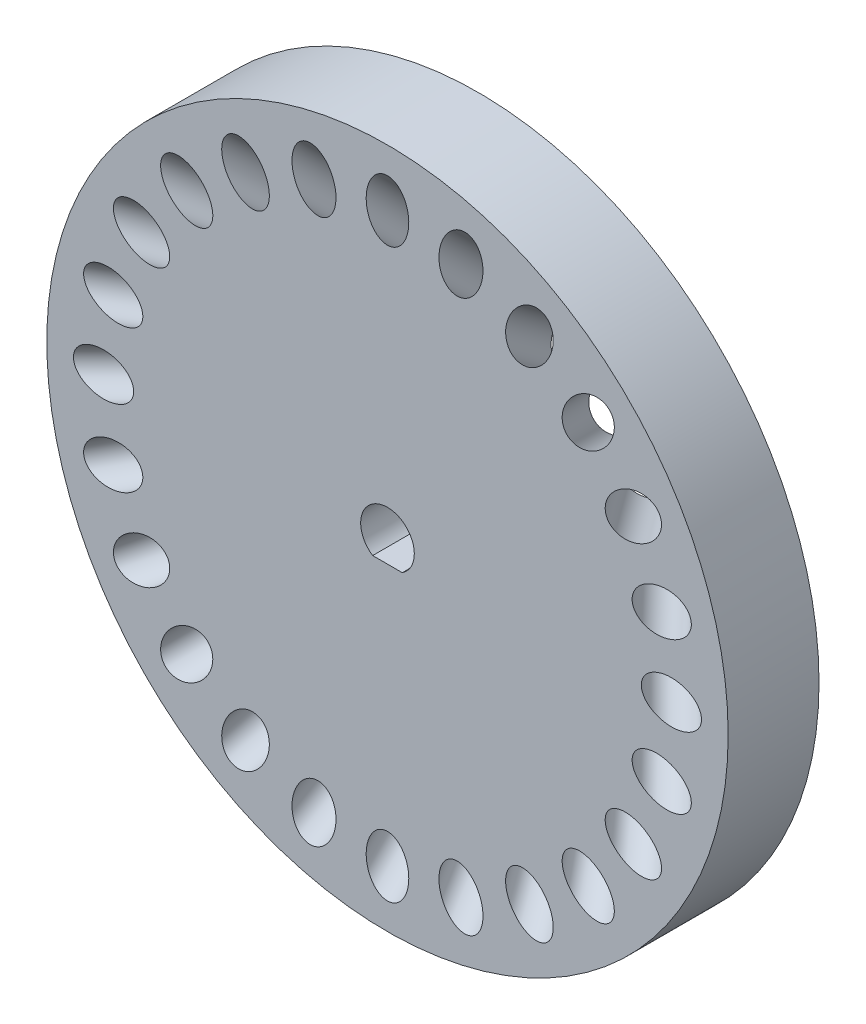
SolidWorks part; units mm, degrees
ref_plane "Front Plane" through (0, 0, 0) normal (0, 0, 1) x (1, 0, 0)
ref_plane "Top Plane" through (0, 0, 0) normal (0, 1, 0) x (1, 0, 0)
ref_plane "Right Plane" through (0, 0, 0) normal (1, 0, 0) x (0, 0, -1)
sketch "Sketch1" plane through (0, 0, 0) normal (0, 0, 1) x (1, 0, 0)
  line L0 (-1.6583, -2.5) -> (1.6583, -2.5)
  arc A0 (1.6583, -2.5) -> (-1.6583, -2.5) centre (0, 0) ccw
  circle A1 centre (0, 0) radius 38.1
  point P1 (0, 38.1)
  dimension "D1" = 6
  dimension "D2" = 76.2
  dimension "D3" = 2.5
extrude "Boss-Extrude1" add sketch "Sketch1" along normal blind 10.16
sketch "Sketch3" plane through (0, 0, 0) normal (1, 0, 0) x (0, 0, -1)
  line L0 (-10.16, 21.59) -> (0, 31.75)
  line L1 (0, 31.75) -> (0, 21.59)
  line L2 (0, 21.59) -> (-10.16, 21.59)
  point P0 (-10.16, 0)
  point P4 (-5.08, 26.67)
  dimension "D1" = 10.16
  dimension "D2" = 10.16
  dimension "D3" = 45
  dimension "D4" = 26.67
ref_plane "Plane1" through (0, 15.875, 15.875) normal (0, -0.7071, -0.7071) x (0, 0.7071, -0.7071)
sketch "Sketch5" plane through (0, 15.875, 15.875) normal (0, -0.7071, -0.7071) x (0, 0.7071, -0.7071)
  circle A0 centre (15.2664, 0) radius 2.3813
  dimension "D1" = 4.7625
extrude "Cut-Extrude1" cut sketch "Sketch5" against normal through all both and the other way through all
pattern_circular "CirPattern1" count 24 every 15 about axis through (0, 0, 10.16) along (0, 0, -1) of "Cut-Extrude1"
